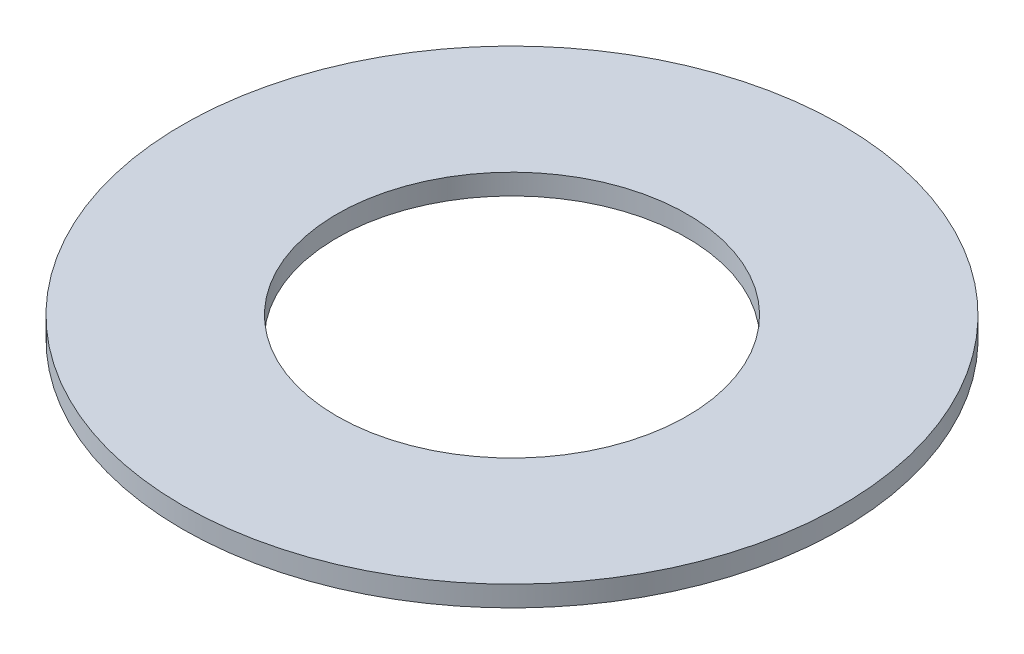
SolidWorks part; units mm, degrees
ref_plane "Front Plane" through (0, 0, 0) normal (0, 0, 1) x (1, 0, 0)
ref_plane "Top Plane" through (0, 0, 0) normal (0, 1, 0) x (1, 0, 0)
ref_plane "Right Plane" through (0, 0, 0) normal (1, 0, 0) x (0, 0, -1)
sketch "Sketch1" plane through (0, 0, 0) normal (0, 1, 0) x (1, 0, 0)
  circle A0 centre (0, 0) radius 80
  dimension "FLANGE_OD" = 160
extrude "Boss-Extrude1" add sketch "Sketch1" along normal blind 5
sketch "Sketch2" plane through (0, 0, 0) normal (0, 1, 0) x (1, 0, 0)
  circle A0 centre (0, 0) radius 42.5
  dimension "BORE_D" = 85
extrude "Cut-Extrude1" cut sketch "Sketch2" along normal through all
sketch "Sketch3" plane through (0, 5, 0) normal (0, 1, 0) x (1, 0, 0)
  circle A0 centre (0, 0) radius 23.5452 construction
  circle A1 centre (-23.5452, 0) radius 3.3521
  dimension "BOLT_D" = 6.7043
  dimension "BOLT_PCD" = 47.0904
extrude "Cut-Extrude2" cut sketch "Sketch3" against normal blind 4.3424 rebuild error yes
pattern_circular "CirPattern1" count 8 over 360 rebuild error yes
